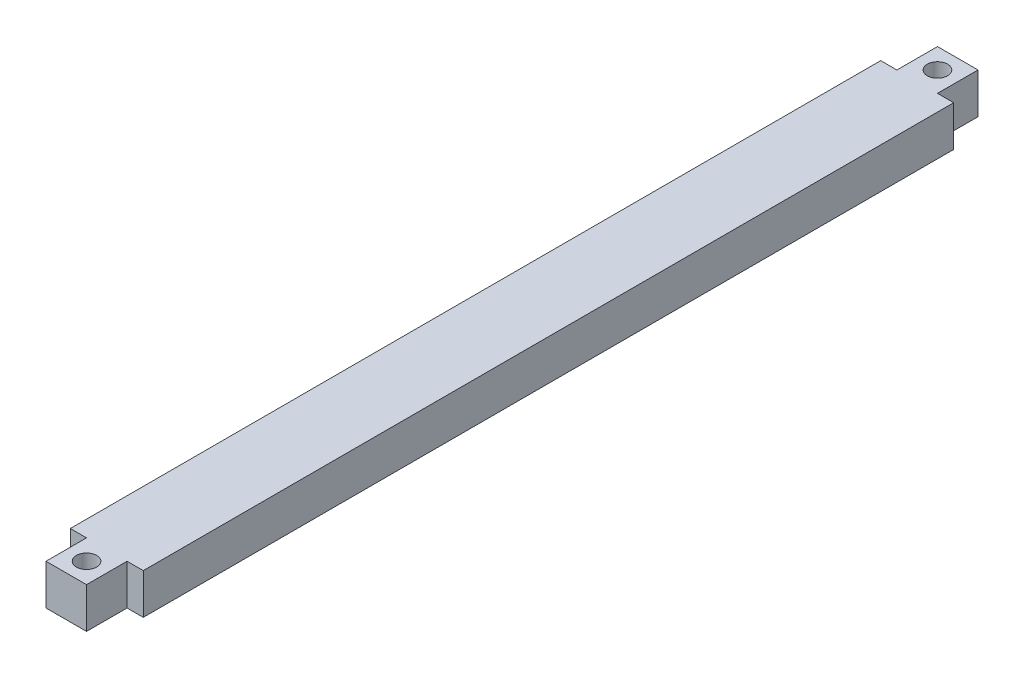
SolidWorks part; units mm, degrees
ref_plane "Front Plane" through (0, 0, 0) normal (0, 0, 1) x (1, 0, 0)
ref_plane "Top Plane" through (0, 0, 0) normal (0, 1, 0) x (1, 0, 0)
ref_plane "Right Plane" through (0, 0, 0) normal (1, 0, 0) x (0, 0, -1)
sketch "Sketch1" plane through (0, 0, 0) normal (0, 0, 1) x (1, 0, 0)
  line L1 (0.4385, 1.0129) -> (5.4385, 1.0129)
  line L2 (0.4385, 1.0129) -> (0.4385, -3.9871)
  line L3 (0.4385, -3.9871) -> (5.4385, -3.9871)
  line L4 (5.4385, 1.0129) -> (5.4385, -3.9871)
  dimension "D1" = 5
  dimension "D2" = 5
extrude "Boss-Extrude1" add sketch "Sketch1" along normal blind 110
sketch "Sketch2" plane through (0, 1.0129, 0) normal (0, 1, 0) x (1, 0, 0)
  line L0 (5.4385, -5) -> (7.4385, -5)
  line L1 (5.4385, -110) -> (5.4385, 0) construction
  line L2 (17.9907, -5) -> (5.4385, -5) construction
  line L3 (7.4385, -5) -> (7.4385, -105)
  line L4 (17.9907, -105) -> (5.4385, -105) construction
  line L5 (7.4385, -105) -> (5.4385, -105)
  line L6 (5.4385, -105) -> (5.4385, -5)
  dimension "D1" = 2
extrude "Boss-Extrude2" add sketch "Sketch2" against normal blind 5
sketch "Sketch3" plane through (0, 1.0129, 0) normal (0, 1, 0) x (1, 0, 0)
  line L0 (0.4385, -5.0091) -> (-1.5615, -5)
  line L1 (0.4385, -110) -> (0.4385, 0) construction
  line L2 (0.4385, -5) -> (-12.1137, -5) construction
  line L3 (-1.5615, -5) -> (-1.5615, -105)
  line L4 (0.4385, -105) -> (-12.1137, -105) construction
  line L5 (-1.5615, -105) -> (0.4385, -105)
  line L6 (0.4385, -105) -> (0.4385, -5.0091)
  dimension "D1" = 2
extrude "Boss-Extrude3" add sketch "Sketch3" against normal blind 5 contours L3 L5 L6 L0
sketch "Sketch4" plane through (0, 1.0129, 0) normal (0, 1, 0) x (1, 0, 0)
  line L0 (5.4385, -2.5) -> (0.4385, -2.5045) construction
  line L1 (5.4385, -5) -> (5.4385, 0) construction
  line L2 (0.4385, -5.0091) -> (0.4385, 0) construction
  line L3 (2.9385, 0) -> (2.9385, -2.5023) construction
  line L4 (5.4385, 0) -> (0.4385, 0) construction
  line L5 (-1.5615, -55) -> (7.4385, -55) construction
  line L6 (-1.5615, -5) -> (-1.5615, -105) construction
  line L7 (7.4385, -105) -> (7.4385, -5) construction
sketch "Sketch5" plane through (7.4385, 0, 0) normal (1, 0, 0) x (0, 0, -1)
  line L0 (-55, 1.0129) -> (-55, -3.9871) construction
  line L1 (-105, -3.9871) -> (-5, -3.9871) construction
ref_plane "Plane1" through (0, 0, 55) normal (0, 0, -1) x (-1, 0, 0)
hole_wizard "M3 Tapped Hole1" positions "Sketch7" profile "Sketch6" tap size "M3" standard "ISO"
sketch "Sketch7" plane through (0, 1.0129, 0) normal (0, 1, 0) x (1, 0, 0)
  point P0 (2.9385, -2.5023)
sketch "Sketch6" plane through (2.9385, 1.0129, 2.5023) normal (1, 0, 0) x (0, 0, 1)
  line L0 (0, 0) -> (0, 8.7511)
  line L1 (0, 8.7511) -> (1.25, 8)
  line L2 (1.25, 8) -> (1.25, 0)
  line L5 (1.25, 0) -> (0, 0)
  line L10 (0, 8.7511) -> (-1.25, 8) construction
  line L11 (0, -6.35) -> (0, 107.95) construction
  dimension "Tap Drill Dia." = 2.5
  dimension "Tap Drill Depth" = 8
  dimension "Drill Angle" = 118
mirror "Mirror1" about plane through (0, 0, 55) normal (0, 0, -1) of "M3 Tapped Hole1"
